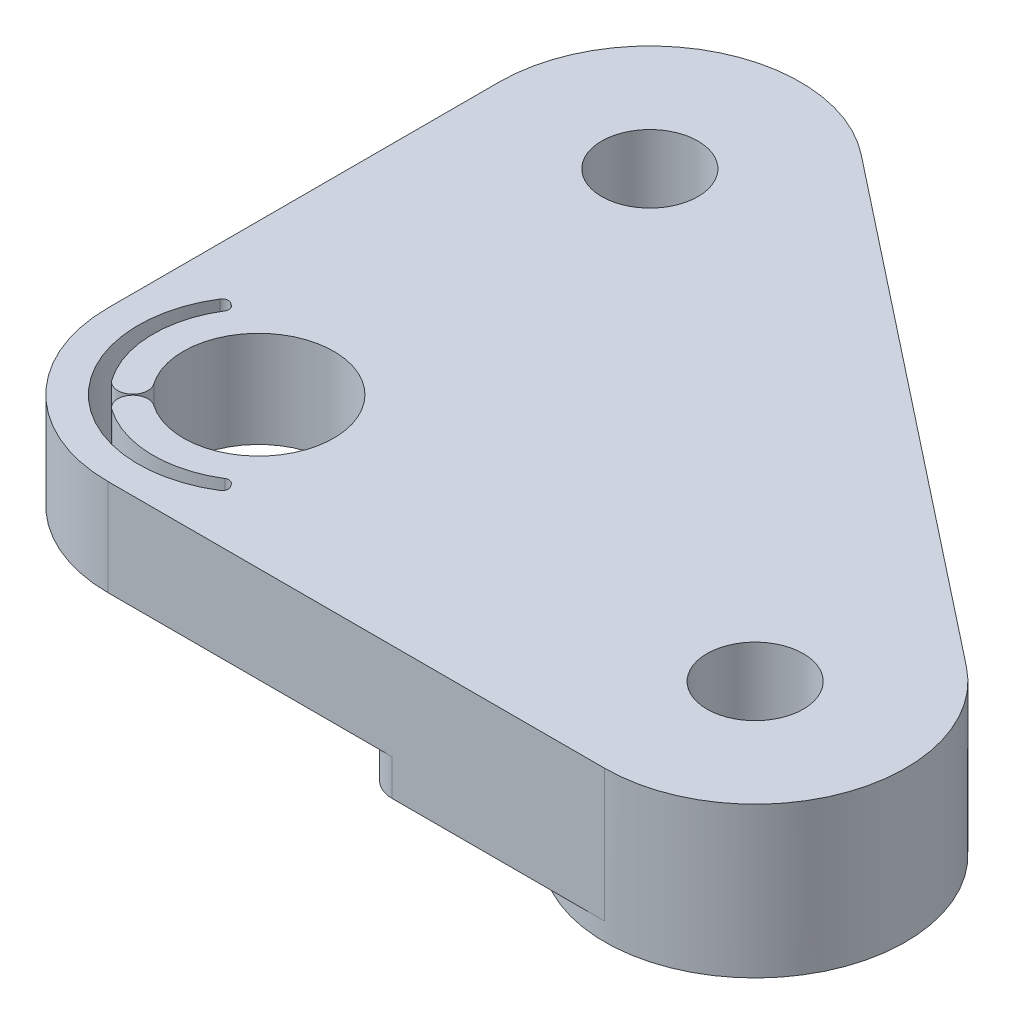
SolidWorks part; units mm, degrees
ref_plane "Front" through (0, 0, 0) normal (0, 0, 1) x (1, 0, 0)
ref_plane "Top" through (0, 0, 0) normal (0, 1, 0) x (1, 0, 0)
ref_plane "Right" through (0, 0, 0) normal (1, 0, 0) x (0, 0, -1)
sketch "Sketch1" plane through (0, 0, 0) normal (0, 1, 0) x (1, 0, 0)
  line L0 (0, 0) -> (16.5, 0) construction
  line L1 (16.5, 0) -> (0, 13) construction
  line L2 (0, 13) -> (0, 0) construction
  line L3 (-5, -5) -> (30.9254, -5)
  line L4 (30.9254, -5) -> (-5, 23.3048)
  line L5 (-5, 23.3048) -> (-5, -5)
  circle A0 centre (16.5, 0) radius 1.6
  circle A1 centre (0, 0) radius 2.5
  circle A2 centre (0, 13) radius 1.6
  dimension "D3" = 5
  dimension "D4" = 3.2
  dimension "D1" = 16.5
  dimension "D2" = 13
  dimension "D5" = 5
extrude "Boss-Extrude1" add sketch "Sketch1" along normal blind 1.57
fillet "Fillet1" radius 5 3 edges at (-5, 0.785, -23.3048) (-5, 0.785, 5) (30.9254, 0.785, 5)
other "Move Face1" [suppressed] offset 0.0762 parameters "D1"=0.0762
sketch "Sketch2" plane through (0, 1.57, 0) normal (0, 1, 0) x (1, 0, 0)
  line L3 (19.5944, 3.9275) -> (3.0944, 16.9275)
  line L4 (-5, 13) -> (-5, 0)
  line L5 (0, -5) -> (16.5, -5)
  line L6 (19.5944, 3.9275) -> (3.0944, 16.9275)
  line L7 (-5, 13) -> (-5, 0)
  line L8 (0, -5) -> (16.5, -5)
  circle A0 centre (0, 0) radius 2.5 construction
  circle A1 centre (16.5, 0) radius 1.6 construction
  circle A2 centre (0, 13) radius 1.6 construction
  arc A3 (3.0944, 16.9275) -> (-5, 13) centre (0, 13) ccw
  arc A4 (-5, 0) -> (0, -5) centre (0, 0) ccw
  arc A5 (16.5, -5) -> (19.5944, 3.9275) centre (16.5, 0) ccw
  arc A6 (3.0944, 16.9275) -> (-5, 13) centre (0, 13) ccw
  arc A7 (-5, 0) -> (0, -5) centre (0, 0) ccw
  arc A8 (16.5, -5) -> (19.5944, 3.9275) centre (16.5, 0) ccw
  circle A9 centre (0, 0) radius 2.5
  circle A10 centre (16.5, 0) radius 1.6
  circle A11 centre (0, 13) radius 1.6
  dimension "D1" = 0
extrude "Boss-Extrude2" add sketch "Sketch2" along normal blind 2.83
sketch "Sketch3" plane through (0, 0, 0) normal (0, -1, 0) x (1, 0, 0)
  circle A0 centre (16.5, 0) radius 5
  circle A1 centre (0, -13) radius 5
  circle A2 centre (0, -13) radius 1.6 construction
  circle A3 centre (16.5, 0) radius 1.6 construction
  circle A4 centre (0, -13) radius 1.6
  circle A5 centre (16.5, 0) radius 1.6
  arc A6 (19.5944, -3.9275) -> (16.5, 5) centre (16.5, 0) ccw construction
  arc A7 (-5, -13) -> (3.0944, -16.9275) centre (0, -13) ccw construction
extrude "Boss-Extrude3" add sketch "Sketch3" along normal blind 0.6
sketch "Sketch4" plane through (0, 4.4, 0) normal (0, 1, 0) x (1, 0, 0)
  line B0 (1.7207, -2.4575) -> (0, 0) construction
  line B1 (2.1191, -3.0264) -> (2.1766, -3.1085)
  line B2 (-3.0264, 2.1191) -> (-3.1085, 2.1766)
  line B3 (-1.7207, -2.4575) -> (0, 0) construction
  arc B4 (2.1187, -3.3928) -> (-3.3928, 2.1187) centre (0, 0) cw
  arc B5 (-1.4339, -2.0479) -> (-2.0075, -2.867) centre (-1.7207, -2.4575) ccw
  arc B6 (-2.0075, -2.867) -> (1.8496, -2.9714) centre (0, 0) ccw
  arc B7 (-2.867, -2.0075) -> (-2.9714, 1.8496) centre (0, 0) cw
  arc B8 (-2.0479, -1.4339) -> (-2.867, -2.0075) centre (-2.4575, -1.7207) cw
  arc B9 (-1.4339, -2.0479) -> (-2.0479, -1.4339) centre (0, 0) cw
  arc B10 (2.1191, -3.0264) -> (1.8496, -2.9714) centre (1.9553, -3.1411) ccw
  arc B11 (2.1766, -3.1085) -> (2.1187, -3.3928) centre (2.0127, -3.2232) cw
  arc B12 (-3.1085, 2.1766) -> (-3.3928, 2.1187) centre (-3.2232, 2.0127) ccw
  arc B13 (-3.0264, 2.1191) -> (-2.9714, 1.8496) centre (-3.1411, 1.9553) cw
sketch_block_instance "5mm_bore_flexure_relief-1"
sketch_block "5mm_bore_flexure_relief" parameters "D4"=2.5, "D6"=0.2, "D1"=80, "D2"=0.5, "D3"=70, "D5"=1
extrude "Cut-Extrude1" cut sketch "Sketch4" against normal blind 10
sketch "Sketch5" plane through (9.4139, 0, -11.9484) normal (0.6189, 0, -0.7855) x (-0.7855, 0, -0.6189)
  line L0 (-12.9606, 0.6) -> (8.0453, 0.6) construction
  line L1 (-12.9606, 4.4) -> (-12.9606, 0) construction
  line L2 (8.0453, 0) -> (8.0453, 4.4) construction
  line L3 (-12.9606, 0) -> (8.0453, 0) construction
  text T0 "LCR-01" font "Century Gothic" height in points 12
  dimension "D1" = 0.6
extrude "Part Num Left" cut sketch "Sketch5" against normal blind 0.4
mirror "Mirror1" [suppressed] of bodies 106 104
delete or keep bodies "Body-Delete/Keep 1" [suppressed] type keep bodies bodies 105
sketch "Sketch6" [suppressed] plane through (-13.2439, 0, -16.8096) normal (-0.6189, 0, -0.7855) x (-0.7855, 0, 0.6189)
  line L0 (-0.1904, 0.6) -> (20.8155, 0.6) construction
  line L1 (-0.1904, 0) -> (-0.1904, 4.4) construction
  line L2 (20.8155, 4.4) -> (20.8155, 0) construction
  line L3 (20.8155, 0) -> (-0.1904, 0) construction
  text T0 "RCR-01" font "Century Gothic" height in points 12
  dimension "D1" = 0.6
extrude "Part Num Right" [suppressed] cut sketch "Sketch6" against normal blind 0.4
sketch "Sketch7" [suppressed] plane through (0, 0, 0) normal (0, -1, 0) x (1, 0, 0)
  circle A0 centre (-10, 0) radius 9.25
extrude "Cut-Extrude2" [suppressed] cut sketch "Sketch7" against normal blind 1.2 and the other way blind 1
fillet "Fillet2" [suppressed] radius 1
sketch "Sketch8" plane through (0, 0, 0) normal (0, -1, 0) x (1, 0, 0)
  circle A0 centre (0, 0) radius 9.25
extrude "Cut-Extrude3" cut sketch "Sketch8" against normal blind 1.2 and the other way blind 1
fillet "Fillet3" radius 1 2 edges at (-5, 0.6, -7.7822) (7.7822, 0.6, 5)
